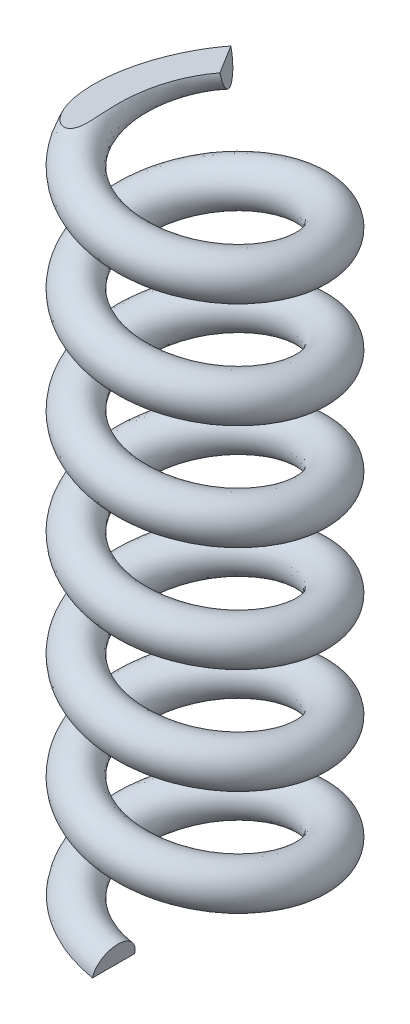
SolidWorks part; units mm, degrees
ref_plane "Front Plane" through (0, 0, 0) normal (0, 0, 1) x (1, 0, 0)
ref_plane "Top Plane" through (0, 0, 0) normal (0, 1, 0) x (1, 0, 0)
ref_plane "Right Plane" through (0, 0, 0) normal (1, 0, 0) x (0, 0, -1)
sketch "Sketch1" plane through (0, 0, 0) normal (0, 1, 0) x (1, 0, 0)
  circle A0 centre (0, 0) radius 4
  dimension "D1" = 8
curve "Helix/Spiral1" pitch 5 height 32 radius 4 left hand yes centre (0, 0, 0) axis (0, 1, 0) start towards (0, 0, 1)
ref_plane "Plane1" through (-2.3511, 32, -3.2361) normal (0.7935, 0.1951, -0.5765) x (-0.5598, -0.1377, -0.8171)
sketch "Sketch2" plane through (-2.3511, 32, -3.2361) normal (0.7935, 0.1951, -0.5765) x (-0.5598, -0.1377, -0.8171)
  circle A0 centre (0.3253, 0.0116) radius 1
  dimension "D1" = 2
sweep "Sweep1" add profiles "Sketch2" path "Helix/Spiral1"
sketch "Sketch3" plane through (4.9543, 1.2183, -3.5998) normal (0.7934, 0.1951, -0.5765) x (-0.5598, -0.1377, -0.8171)
  line L0 (-0.12, 31.6481) -> (-1.12, 31.6481) construction
  line L2 (-1.12, 31.6481) -> (2.9015, 31.6481)
  line L4 (-1.12, 34.01) -> (2.9015, 34.01)
  line L5 (2.9015, 31.6481) -> (2.9015, 34.01)
  line L6 (-1.12, 31.6481) -> (-3.5352, 31.6481)
  line L8 (-1.12, 34.01) -> (-3.5352, 34.01)
  line L10 (-3.5352, 31.6481) -> (-5.0146, 31.6481)
  line L12 (-3.5352, 34.01) -> (-5.0146, 34.01)
  line L14 (-5.0146, 31.6481) -> (-7.6453, 31.6481)
  line L16 (-5.0146, 34.01) -> (-7.6453, 34.01)
  line L17 (-7.6453, 31.6481) -> (-7.6453, 34.01)
  circle A0 centre (-0.12, 31.6481) radius 1 construction
extrude "Cut-Extrude2" cut sketch "Sketch3" against normal blind 10
sketch "Sketch5" plane through (0, 0, 0) normal (0.9808, -0.1951, 0) x (0, 0, -1)
  line L0 (-10.7201, -0.0342) -> (6.653, -0.0342)
extrude "Cut-Extrude4" cut sketch "Sketch5" against normal through all and the other way through all flip side to cut
